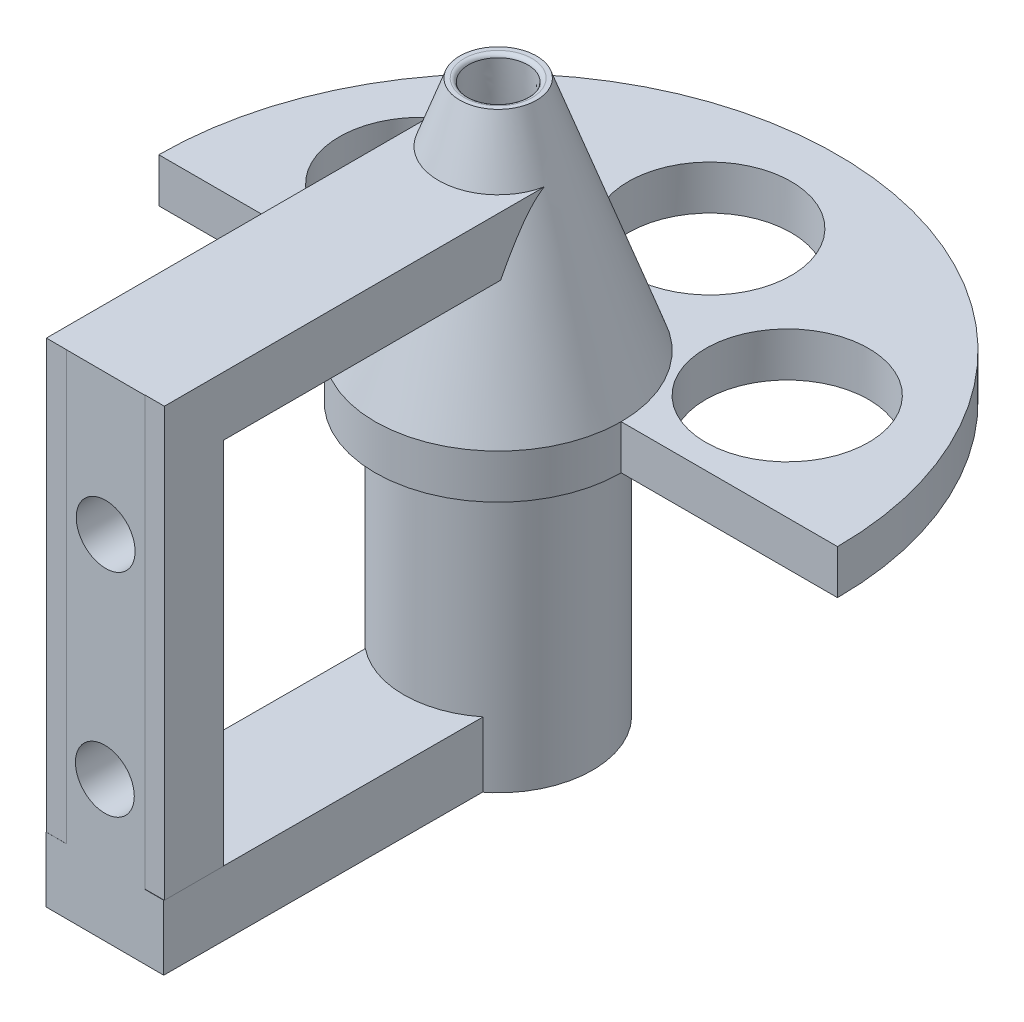
SolidWorks part; units mm, degrees
ref_plane "Front Plane" through (0, 0, 0) normal (0, 0, 1) x (1, 0, 0)
ref_plane "Top Plane" through (0, 0, 0) normal (0, 1, 0) x (1, 0, 0)
ref_plane "Right Plane" through (0, 0, 0) normal (1, 0, 0) x (0, 0, -1)
sketch "Sketch2" plane through (0, 0, 0) normal (0, 0, 1) x (1, 0, 0)
  line L0 (2, 0) -> (2.6, 0)
  line L2 (2, 0) -> (2, -16)
  line L3 (2, -16) -> (3.4, -16)
  line L4 (2.6, 0) -> (8.3409, -16)
  line L8 (3.4, -16) -> (3.4, -37.4278)
  line L9 (0, 0) -> (0, -37.4278) construction
  line L10 (6.4, -19) -> (6.4, -37.4278)
  line L12 (8.3409, -16) -> (20.3409, -16)
  line L13 (3.4, -37.4278) -> (6.4, -37.4278)
  line L14 (20.3409, -16) -> (20.3409, -19)
  line L15 (20.3409, -19) -> (6.4, -19)
revolve "Revolve1" add sketch "Sketch2" angle 360 about L9
fillet "Fillet1" radius 0.3 1 edges at (0, 0, 2)
sketch "Sketch3" plane through (0, -37.4278, 0) normal (0, -1, 0) x (1, 0, 0)
  circle A0 centre (0, 0) radius 3.6
extrude "Cut-Extrude1" cut sketch "Sketch3" along normal blind 1 and the other way blind 22
fillet "Fillet2" radius 0.5 1 edges at (0, -15.4278, -2)
fillet "Fillet3" radius 0.5 1 edges at (0, -37.4278, 3.6)
ref_plane "Plane2" through (0, -16, 0) normal (0, 1, 0) x (1, 0, 0)
ref_plane "Plane3" through (0, -19, 0) normal (0, -1, 0) x (-1, 0, 0)
sketch "Sketch5" plane through (0, -16, 0) normal (0, 1, 0) x (1, 0, 0)
  line L2 (-3.25, -14) -> (3.25, -14)
  line L3 (-3.25, -14) -> (-3.25, -16)
  line L4 (-3.25, -16) -> (3.25, -16)
  line L5 (3.25, -14) -> (3.25, -16)
sketch "Sketch6" plane through (0, -19, 0) normal (0, -1, 0) x (1, 0, 0)
  line L2 (4.25, 14) -> (-4.25, 14)
  line L3 (4.25, 14) -> (4.25, 16)
  line L4 (4.25, 16) -> (-4.25, 16)
  line L5 (-4.25, 14) -> (-4.25, 16)
loft "Cut-Loft2" cut profiles "Sketch5", "Sketch6" connector at (3.25, -16, 16) connector at (4.25, -19, 16)
sketch "Sketch7" plane through (0, -16, 0) normal (0, 1, 0) x (1, 0, 0)
  line L1 (-3.25, -13.5) -> (3.25, -13.5)
  line L2 (-3.25, -13.5) -> (-3.25, -16.5)
  line L3 (-3.25, -16.5) -> (3.25, -16.5)
  line L4 (3.25, -13.5) -> (3.25, -16.5)
sketch "Sketch8" plane through (0, -19, 0) normal (0, -1, 0) x (1, 0, 0)
  line L1 (4.25, 13.5) -> (-4.25, 13.5)
  line L2 (4.25, 13.5) -> (4.25, 16.5)
  line L3 (4.25, 16.5) -> (-4.25, 16.5)
  line L4 (-4.25, 13.5) -> (-4.25, 16.5)
loft "Cut-Loft3" cut profiles "Sketch8", "Sketch7" connector at (4.25, -19, 16.5) connector at (3.25, -16, 16.5)
sketch "Sketch11" plane through (0, -16, 0) normal (0, 1, 0) x (1, 0, 0)
  line L0 (0, 0) -> (-17.6157, 10.1705)
  line L1 (-17.6157, 10.1705) -> (-12.4196, 7.1705)
  circle A0 centre (0, 0) radius 20.3409 construction
  circle A1 centre (-12.4196, 7.1705) radius 5.52
  circle A2 centre (0, 14.3409) radius 5.52
  circle A3 centre (12.4196, 7.1705) radius 5.52
  point P13 (0, 0)
  dimension "D1" = 3
extrude "Cut-Extrude3" cut sketch "Sketch11" against normal blind 10 contours A2 | A3 | L0 A1 | L0 A1 region at (-13.591, -16, -5.1416) region at (-11.2482, -16, -9.1993) region at (0, -16, -14.3409) region at (12.4196, -16, -7.1705)
sketch "Sketch13" plane through (0, -16, 0) normal (0, 1, 0) x (1, 0, 0)
  line L0 (-8.3409, 0) -> (-20.3409, 0)
  line L1 (8.3409, 0) -> (20.3409, 0)
  line L2 (-10.1705, -17.6157) -> (-4.1705, -7.2234)
  line L3 (9.9324, -17.7511) -> (4.0728, -7.2789)
  circle A0 centre (0, 0) radius 20.3409 construction
  arc A1 (20.3409, 0) -> (9.9324, -17.7511) centre (0, 0) cw
  arc A2 (-20.3409, 0) -> (-10.1705, -17.6157) centre (0, 0) ccw
  circle A3 centre (0, 0) radius 8.3409 construction
  arc A4 (-4.1705, -7.2234) -> (-8.3409, 0) centre (0, 0) cw
  arc A5 (4.0728, -7.2789) -> (8.3409, 0) centre (0, 0) ccw
extrude "Cut-Extrude4" cut sketch "Sketch13" against normal blind 10
sketch "Sketch14" plane through (0, -16, 0) normal (0, 1, 0) x (1, 0, 0)
  line L0 (0, 0) -> (23, 0)
  line L1 (0, 0) -> (-23, 0)
  line L2 (0, 0) -> (0, 23)
  line L3 (0, 0) -> (-20.17, 0)
  line L4 (0, 0) -> (20.17, 0)
  line L5 (0, 0) -> (0, 20.17)
  arc A0 (23, 0) -> (-23, 0) centre (0, 0) ccw
  arc A1 (-20.17, 0) -> (20.17, 0) centre (0, 0) cw
  arc M7 (20.3409, 0) -> (-20.3409, 0) centre (0, 0) ccw
extrude "Boss-Extrude1" add sketch "Sketch14" against normal blind 3 contours L0 A0 L2 M7 | L2 A0 L1 M7 region at (14.6132, -16, -14.6132) region at (-21.6705, -16, -0.3253)
sketch "Sketch15" plane through (0, -16, 0) normal (0, 1, 0) x (1, 0, 0)
  line L0 (-10.1705, -17.6157) -> (-8.3409, 0)
  line L1 (9.9324, -17.7511) -> (8.3409, 0)
  line L2 (9.9324, -17.7511) -> (0.2611, -9.6713)
  line L3 (0.2611, -9.6713) -> (-10.1705, -17.6157)
  arc A0 (8.3409, 0) -> (-8.3409, 0) centre (0, 0) cw
extrude "Boss-Extrude4" add sketch "Sketch15" against normal blind 3
sketch "Sketch21" plane through (0, -16, 0) normal (0, 1, 0) x (1, 0, 0)
  line L0 (9.9324, -17.7511) -> (8.3409, 0) construction
  line L1 (8.3409, 0) -> (11.0372, -19.0718)
  line L2 (11.0372, -19.0718) -> (-8.9098, -24.215)
  line L3 (-8.9098, -24.215) -> (-14.9339, -10.9919)
  line L4 (-14.9339, -10.9919) -> (-8.3409, 0)
  arc A0 (-8.3409, 0) -> (8.3409, 0) centre (0, 0) ccw
  arc A1 (-8.3409, 0) -> (8.3409, 0) centre (0, 0) ccw construction
extrude "Cut-Extrude5" cut sketch "Sketch21" against normal blind 4
sketch "Sketch22" plane through (0, 0, 0) normal (0, 0, 1) x (1, 0, 0)
  line L4 (2, -16) -> (2, -19)
  line L5 (-17.2375, -19) -> (17.2375, -19) construction
  line L6 (-2, -16) -> (2, -16)
  line L10 (-2, -16) -> (-2, -19)
  line L11 (-2, -19) -> (2, -19)
extrude "Boss-Extrude6" add sketch "Sketch22" along normal blind 15
sketch "Sketch25" plane through (0, -15.4278, 0) normal (0, -1, 0) x (1, 0, 0)
  circle A0 centre (0, 0) radius 3.6
extrude "Cut-Extrude6" cut sketch "Sketch25" along normal blind 21
sketch "Sketch26" plane through (0, 0, 15) normal (0, 0, 1) x (1, 0, 0)
  line L7 (-2.5, -16) -> (2.5, -16)
  line L8 (-2.5, -16) -> (-2.5, -40)
  line L9 (-2.5, -40) -> (2.5, -40)
  line L10 (2.5, -16) -> (2.5, -40)
extrude "Boss-Extrude7" add sketch "Sketch26" along normal blind 3 and the other way blind 0.5
sketch "Sketch27" plane through (0, 0, 18) normal (0, 0, 1) x (1, 0, 0)
  circle A0 centre (0, -23) radius 1.5
  circle A1 centre (0, -36) radius 1.5
extrude "Cut-Extrude8" cut sketch "Sketch27" against normal blind 3.5
sketch "Sketch28" plane through (0, -16, 0) normal (0, 1, 0) x (1, 0, 0)
  line L0 (-2, -8.0976) -> (-5.7865, -17.9107)
  line L1 (-5.7865, -17.9107) -> (0.5181, -20.0204)
  line L2 (0.5181, -20.0204) -> (6.4639, -17.7319)
  line L3 (6.4639, -17.7319) -> (2, -8.0976)
  arc A0 (-2, -8.0976) -> (2, -8.0976) centre (0, 0) ccw
extrude "Cut-Extrude9" cut sketch "Sketch28" against normal blind 25
ref_plane "Plane4" through (0, -8, 0) normal (0, 1, 0) x (1, 0, 0)
sketch "Sketch32" plane through (0, -8, 0) normal (0, 1, 0) x (1, 0, 0)
  line L0 (2.65, -4.5899) -> (2.65, -24.5899)
  line L1 (-2.6753, -4.5752) -> (-2.6753, -24.5752)
  line L2 (-2.6753, -24.5752) -> (2.65, -24.5899)
  arc A0 (-0.0293, -5.2999) -> (2.65, -4.5899) centre (0, 0) ccw
  arc A1 (-0.0293, -5.2999) -> (-2.6753, -4.5752) centre (0, 0) cw
sketch3d "3DSketch8"
  line L0 (-2.6753, -8, 4.5752) -> (-2.6619, -16, 7.9047)
  line L1 (2.65, -8, 4.5899) -> (2.645, -16, 7.9104)
  arc A0 (-8.3409, -16, 0) -> (8.3409, -16, 0) centre (0, -16, 0) ccw construction
  point P6 (0, -7.6591, 0)
extrude "Boss-Extrude8" add sketch "Sketch32" along normal blind 4 contours L0 L2 L1 A1 A0
sketch "Sketch37" plane through (0, -4, 0) normal (0, 1, 0) x (1, 0, 0)
  circle A0 centre (0, 0) radius 3.9
sketch3d "3DSketch10"
  line L0 (2.65, -8, 4.7857) -> (2.6512, -4, 2.8603)
  line L1 (-2.6753, -8, 4.7716) -> (-2.6764, -4, 2.8367)
  circle A0 centre (0, -4, 0) radius 3.9 construction
  point P5 (0, -0.1, 0)
sketch "Sketch41" plane through (2.65, 0, 0) normal (1, 0, 0) x (0, 0, -1)
  line L0 (-4.7857, -8) -> (-6.7287, -4)
  line L1 (-4.5899, -4) -> (-24.5899, -4) construction
  line L4 (-1.6716, -4.2547) -> (-4.7857, -8)
  line L5 (-6.7287, -4) -> (-1.3138, -4)
  line L6 (-1.3138, -4) -> (-1.6716, -4.2547)
extrude "Boss-Extrude13" add sketch "Sketch41" against normal blind 5.3253
sketch "Sketch44" plane through (-0.0679, 0, 24.5824) normal (-0.0028, 0, 1) x (1, 0, 0.0028)
  line L1 (-2.6074, -4) -> (2.7179, -4)
  line L2 (-2.6074, -4) -> (-2.6074, -37.3539)
  line L3 (-2.6074, -37.3539) -> (2.7179, -37.3539)
  line L4 (2.7179, -4) -> (2.7179, -37.3539)
extrude "Boss-Extrude14" add sketch "Sketch44" along normal blind 2 and the other way blind 2
sketch "Sketch45" plane through (-0.0734, 0, 26.5824) normal (-0.0028, 0, 1) x (1, 0, 0.0028)
  line L1 (-4, -33) -> (4, -33)
  line L2 (-4, -33) -> (-4, -37.4)
  line L3 (-4, -37.4) -> (4, -37.4)
  line L4 (4, -33) -> (4, -37.4)
extrude "Boss-Extrude15" add sketch "Sketch45" against normal blind 22
sketch "Sketch47" plane through (0, -33, 0) normal (0, 1, 0) x (1, 0, 0)
  line L1 (3.95, -22.57) -> (-4.05, -22.57)
  line L2 (3.95, -22.57) -> (3.95, -26.57)
  line L3 (3.95, -26.57) -> (-4.05, -26.57)
  line L4 (-4.05, -22.57) -> (-4.05, -26.57)
extrude "Boss-Extrude16" add sketch "Sketch47" along normal blind 29
sketch "Sketch48" plane through (0, 0, 22.57) normal (0, 0, -1) x (-1, 0, 0)
  line L0 (-3.95, -4) -> (-3.95, -33) construction
  line L1 (4.05, -4) -> (-3.95, -4)
  line L2 (4.05, -4) -> (4.05, -8)
  line L3 (4.05, -8) -> (-3.95, -8)
  line L4 (-3.95, -4) -> (-3.95, -8)
extrude "Boss-Extrude17" add sketch "Sketch48" along normal blind 23
sketch "Sketch49" plane through (0, -15.4278, 0) normal (0, -1, 0) x (1, 0, 0)
  circle A0 centre (0, 0) radius 3.6
sketch "Sketch51" plane through (0, 0, 0) normal (0, 1, 0) x (1, 0, 0)
  circle A0 centre (0, 0) radius 2.0017
loft "Cut-Loft5" cut profiles "Sketch49", "Sketch51" connector at (-2.8166, -15.4278, 2.242) connector at (-0.1671, 0, 1.9947)
sketch "Sketch52" plane through (-0.0734, 0, 26.5824) normal (-0.0028, 0, 1) x (1, 0, 0.0028)
  line L0 (2.7179, -4) -> (-2.6074, -4) construction
  line L1 (0.0552, -4) -> (0.0552, -13.5)
  line L2 (0, -37.4) -> (0, -27.9)
  line L3 (-4, -37.4) -> (4, -37.4) construction
  circle A0 centre (0.0552, -13.5) radius 2
  circle A1 centre (0, -27.9) radius 2
extrude "Cut-Extrude10" cut sketch "Sketch52" against normal blind 4.1 contours A0 | A1 region at (-1.3924, -14.8742, 26.5788) region at (1.3008, -29.2742, 26.5862)
